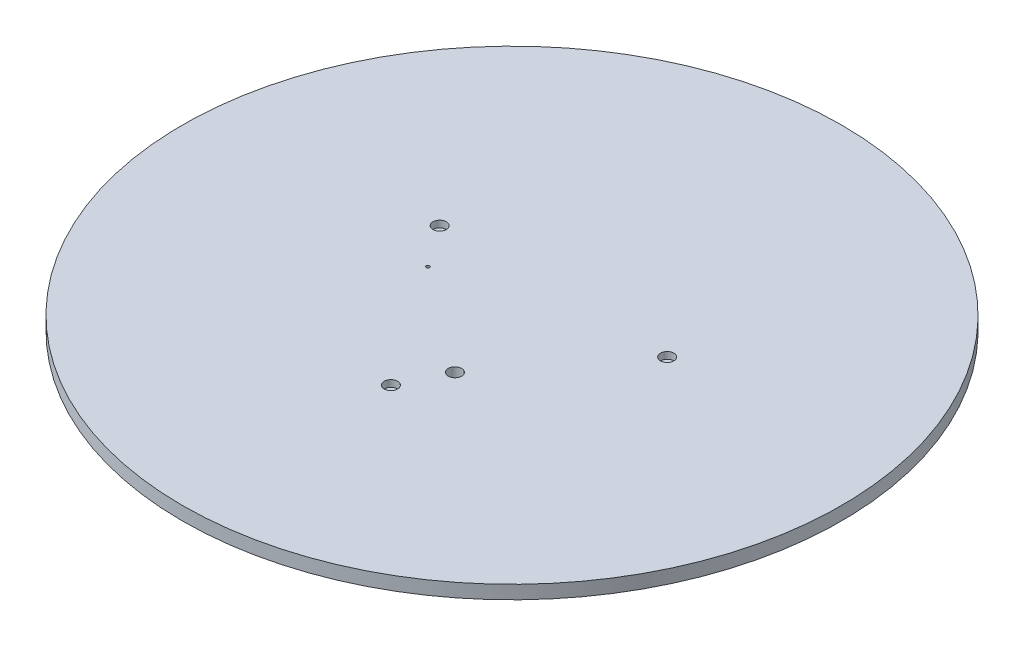
SolidWorks part; units mm, degrees
material "PTFE (general)"
ref_plane "Front Plane" through (0, 0, 0) normal (0, 0, 1) x (1, 0, 0)
ref_plane "Top Plane" through (0, 0, 0) normal (0, 1, 0) x (1, 0, 0)
ref_plane "Right Plane" through (0, 0, 0) normal (1, 0, 0) x (0, 0, -1)
sketch "Sketch1" plane through (0, 0, 0) normal (0, 1, 0) x (1, 0, 0)
  circle A0 centre (0, 0) radius 49
  dimension "D2" = 98
extrude "Boss-Extrude1" add sketch "Sketch1" along normal blind 2
sketch "Sketch2" plane through (0, 2, 0) normal (0, 1, 0) x (1, 0, 0)
  line L0 (8.6667, 0) -> (-17.7957, 0) construction
  line L1 (-17.7957, 0) -> (0, 0) construction
  line L2 (-12.5, 0) -> (0, 0) construction
  circle A2 centre (-12.5, 0) radius 0.25
  dimension "D1" = 0.5
  dimension "D2" = 12.5
  dimension "D5" = 0
extrude "Cut-Extrude1" cut sketch "Sketch2" against normal through all both and the other way through all
sketch "Sketch3" plane through (0, 2, 0) normal (0, 1, 0) x (1, 0, 0)
  line L1 (0, 0) -> (0, 12.5) construction
  line L2 (0, 12.5) -> (0, 0) construction
  line L3 (0, 0) -> (7.8426, -29.2691) construction
  circle A1 centre (3.1058, -11.5911) radius 1
  dimension "D3" = 2
  dimension "D4" = 12
  dimension "D5" = 15
extrude "Cut-Extrude2" cut sketch "Sketch3" against normal through all both and the other way through all
sketch "Sketch4" plane through (0, 2, 0) normal (0, 1, 0) x (1, 0, 0)
  line L0 (-16.9145, 6.1564) -> (0, 0) construction
  line L1 (0, 0) -> (0, -18) construction
  line L2 (0, -18) -> (0, 0) construction
  line L3 (0, 0) -> (16.9145, 6.1564) construction
  circle A0 centre (0, 0) radius 18
  circle A1 centre (0, -18) radius 1
  circle A2 centre (-16.9145, 6.1564) radius 1
  circle A3 centre (16.9145, 6.1564) radius 1
  dimension "D1" = 2
  dimension "D2" = 2
  dimension "D3" = 2
  dimension "D4" = 36
  dimension "D5" = 110
  dimension "D6" = 140
extrude "Cut-Extrude3" cut sketch "Sketch4" against normal blind 1 contours A1 | A2 | A3
